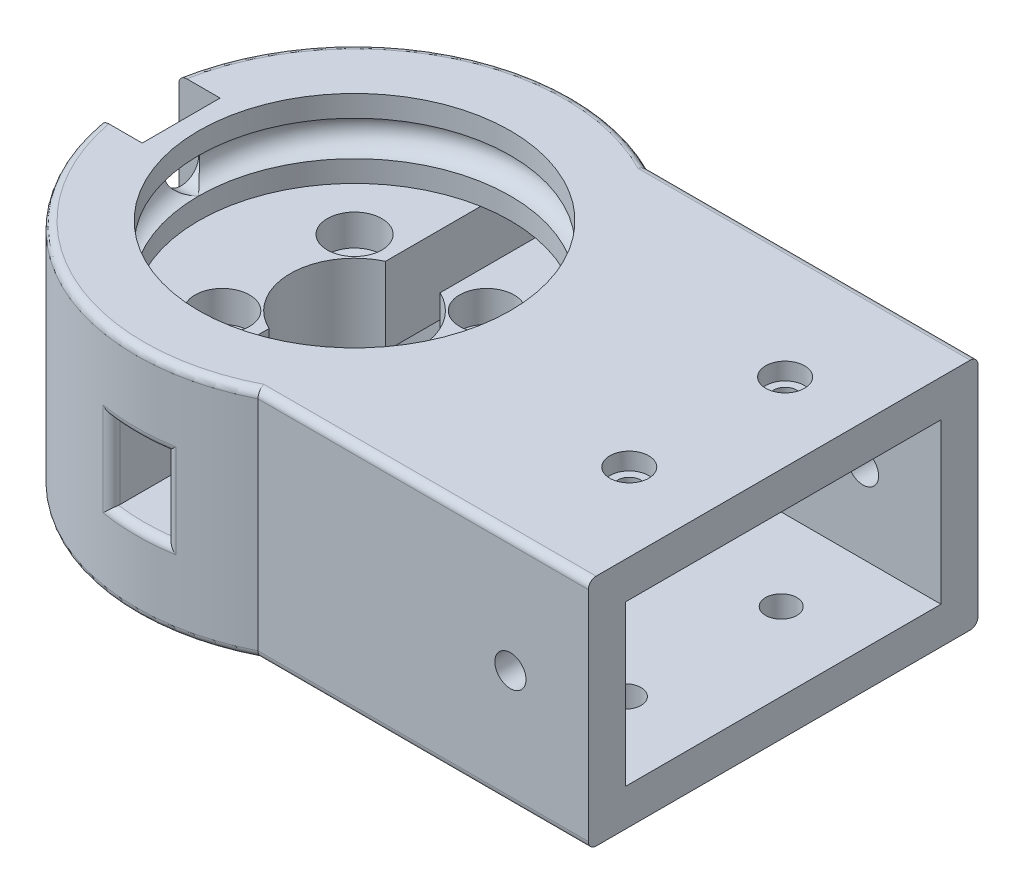
SolidWorks part; units mm, degrees
ref_plane "Front" through (0, 0, 0) normal (0, 0, 1) x (1, 0, 0)
ref_plane "Top" through (0, 0, 0) normal (0, 1, 0) x (1, 0, 0)
ref_plane "Right" through (0, 0, 0) normal (1, 0, 0) x (0, 0, -1)
sketch "Sketch1" plane through (0, 0, 0) normal (0, 0, 1) x (1, 0, 0)
  line L0 (0, -2.25) -> (0, -5)
  line L1 (0, 2.25) -> (0, 5)
  line L2 (0, 5) -> (8, 5)
  line L3 (8, 5) -> (8, -5)
  line L4 (8, -5) -> (0, -5)
  line L6 (-20, 9.1279) -> (-20, -8.1657) construction
  arc A0 (0, -2.25) -> (0, 2.25) centre (0, 0) ccw
revolve "Revolve1" add sketch "Sketch1" angle 360 about L6
sketch "Sketch2" plane through (0, -5, 0) normal (0, -1, 0) x (1, 0, 0)
  circle A0 centre (-20, 0) radius 28
extrude "Boss-Extrude1" add sketch "Sketch2" along normal blind 20
sketch "Sketch3" plane through (0, -25, 0) normal (0, -1, 0) x (1, 0, 0)
  line L1 (-7.3905, 25) -> (45, 25)
  line L3 (-7.3905, -25) -> (45, -25)
  line L4 (45, 25) -> (45, -25)
  arc A0 (-7.3905, -25) -> (-7.3905, 25) centre (-20, 0) ccw
  point P0 (-20, 0)
extrude "Boss-Extrude2" add sketch "Sketch3" against normal blind 30
sketch "Sketch4" plane through (45, 0, 0) normal (1, 0, 0) x (0, 0, -1)
  line L4 (-20.25, 0.25) -> (20.25, 0.25)
  line L5 (-20.25, 0.25) -> (-20.25, -20.25)
  line L6 (-20.25, -20.25) -> (20.25, -20.25)
  line L7 (20.25, 0.25) -> (20.25, -20.25)
  point P6 (0, -10)
extrude "Cut-Extrude2" cut sketch "Sketch4" against normal blind 40
sketch "Sketch5" plane through (0, 5, 0) normal (0, 1, 0) x (1, 0, 0)
  line L0 (45, 25) -> (35, 25)
  line L1 (-7.3905, 25) -> (45, 25) construction
  line L2 (35, 25) -> (35, -25)
  line L3 (45, -25) -> (-7.3905, -25) construction
  line L4 (35, -25) -> (45, -25)
  line L5 (45, -25) -> (45, 25)
extrude "Cut-Extrude3" cut sketch "Sketch5" against normal blind 40
sketch "Sketch6" plane through (0, -20.25, 0) normal (0, 1, 0) x (1, 0, 0)
  circle A0 centre (25, 9.75) radius 2
  circle A1 centre (25, -10.25) radius 2
extrude "Cut-Extrude4" cut sketch "Sketch6" against normal blind 40 and the other way blind 40
sketch "Sketch7" plane through (0, 0, 20.25) normal (0, 0, -1) x (-1, 0, 0)
  circle A0 centre (-25, -10) radius 2
extrude "Cut-Extrude5" cut sketch "Sketch7" against normal blind 45 and the other way blind 50
sketch "Sketch9" plane through (0, -25, 0) normal (0, -1, 0) x (1, 0, 0)
  circle A0 centre (-20, 0) radius 16.5
extrude "Cut-Extrude6" cut sketch "Sketch9" against normal blind 10
sketch "Sketch10" plane through (0, -15, 0) normal (0, -1, 0) x (1, 0, 0)
  circle A0 centre (-20, 0) radius 8.5
extrude "Cut-Extrude7" cut sketch "Sketch10" against normal blind 10
sketch "Sketch11" plane through (0, -15, 0) normal (0, -1, 0) x (1, 0, 0)
  circle A1 centre (-28.4853, 8.4853) radius 2
  circle A2 centre (-28.4853, -8.4853) radius 2
  circle A3 centre (-11.5147, -8.4853) radius 2
  circle A4 centre (-11.5147, 8.4853) radius 2
extrude "Cut-Extrude8" cut sketch "Sketch11" against normal blind 10
sketch "Sketch12" plane through (0, -5, 0) normal (0, 1, 0) x (1, 0, 0)
  circle A0 centre (-28.4853, 8.4853) radius 3.4
  circle A1 centre (-28.4853, -8.4853) radius 3.4
  circle A2 centre (-11.5147, -8.4853) radius 3.4
  circle A3 centre (-11.5147, 8.4853) radius 3.4
extrude "Cut-Extrude10" cut sketch "Sketch12" against normal blind 4
sketch "Sketch14" plane through (0, -5, 0) normal (0, 1, 0) x (1, 0, 0)
  line L1 (-16.5, 30.8966) -> (-23.5, 30.8966)
  line L2 (-16.5, 30.8966) -> (-16.5, -30.8966)
  line L3 (-16.5, -30.8966) -> (-23.5, -30.8966)
  line L4 (-23.5, 30.8966) -> (-23.5, -30.8966)
  line L5 (-16.5, 30.8966) -> (-23.5, -30.8966) construction
  line L6 (-16.5, -30.8966) -> (-23.5, 30.8966) construction
  point P0 (-20, 0)
extrude "Cut-Extrude11" cut sketch "Sketch14" against normal blind 10
ref_plane "Plane2" through (-42.25, 0, 0) normal (1, 0, 0) x (0, 0, -1)
sketch "Sketch15" plane through (0, 0, 0) normal (1, 0, 0) x (0, 0, -1)
  circle A0 centre (0, 0) radius 2.25
extrude "Cut-Extrude12" cut sketch "Sketch15" against normal blind 50
sketch "Sketch16" plane through (-42.25, 0, 0) normal (1, 0, 0) x (0, 0, -1)
  line L1 (5, 31.8439) -> (-5, 31.8439)
  line L2 (5, 31.8439) -> (5, -31.8439)
  line L3 (5, -31.8439) -> (-5, -31.8439)
  line L4 (-5, 31.8439) -> (-5, -31.8439)
  line L5 (5, 31.8439) -> (-5, -31.8439) construction
  line L6 (5, -31.8439) -> (-5, 31.8439) construction
  point P0 (0, 0)
extrude "Cut-Extrude13" cut sketch "Sketch16" against normal blind 50
sketch "Sketch17" plane through (-42.25, 0, 0) normal (-1, 0, 0) x (0, 0, 1)
  line L0 (0, -25) -> (0, -22) construction
  line L1 (5, -25) -> (-5, -25) construction
  circle A0 centre (0, -22) radius 1.5
extrude "Cut-Extrude15" cut sketch "Sketch17" against normal blind 10
sketch "Sketch18" plane through (0, -25, 0) normal (0, -1, 0) x (1, 0, 0)
  circle A0 centre (-20, 0) radius 16.5
  circle A1 centre (-20, 0) radius 16.25
extrude "Boss-Extrude3" add sketch "Sketch18" against normal blind 10
sketch "Sketch19" plane through (0, -15, 0) normal (0, -1, 0) x (1, 0, 0)
  circle A0 centre (-20, 0) radius 8.5
  circle A1 centre (-20, 0) radius 8.25
extrude "Boss-Extrude4" add sketch "Sketch19" against normal blind 10
sketch "Sketch20" plane through (0, -15, 0) normal (0, -1, 0) x (1, 0, 0)
  line L0 (-16.5, -7.746) -> (-16.5, -15.8686) construction
  line L1 (-23.5, 10.3322) -> (-16.5, 10.3322)
  line L2 (-23.5, 10.3322) -> (-23.5, -10.3322)
  line L3 (-23.5, -10.3322) -> (-16.5, -10.3322)
  line L4 (-16.5, 10.3322) -> (-16.5, -10.3322)
  line L5 (-23.5, 10.3322) -> (-16.5, -10.3322) construction
  line L6 (-23.5, -10.3322) -> (-16.5, 10.3322) construction
  point P0 (-20, 0)
extrude "Cut-Extrude16" cut sketch "Sketch20" against normal blind 10
sketch "Sketch21" plane through (0, -5, 0) normal (0, 1, 0) x (1, 0, 0)
  circle A0 centre (-11.5147, 8.4853) radius 3.5
  circle A1 centre (-28.4853, 8.4853) radius 3.5
  circle A2 centre (-28.4853, -8.4853) radius 3.5
  circle A3 centre (-11.5147, -8.4853) radius 3.5
extrude "Cut-Extrude17" cut sketch "Sketch21" against normal blind 4
fillet "Fillet1" radius 1 17 edges at (-20, -25, -16.25) (-32.4822, -25, -25.0638) (-32.4822, -25, 25.0638) (-32.4822, 5, 25.0638) (-32.4822, 5, -25.0638) (-20, -5, -28) (-16.5, -10, -27.7804) (-20, -15, -28) (-23.5, -10, -27.7804) (-20, -5, 28) (-23.5, -10, 27.7804) (-20, -15, 28) (-16.5, -10, 27.7804) (13.8048, -25, 25) (13.8048, -25, -25) (13.8048, 5, -25) (13.8048, 5, 25)
sketch "Sketch23" plane through (0, 5, 0) normal (0, 1, 0) x (1, 0, 0)
  circle A0 centre (25, 9.75) radius 2
  circle A1 centre (25, -10.25) radius 2
extrude "Boss-Extrude5" add sketch "Sketch23" against normal blind 4.75
sketch "Sketch24" plane through (0, 0.25, 0) normal (0, -1, 0) x (1, 0, 0)
  line L0 (35, -20.25) -> (35, -10.25) construction
  line L1 (35, -20.25) -> (35, 20.25) construction
  line L2 (35, -10.25) -> (25, -10.25) construction
  line L3 (25, -10.25) -> (25, 9.75) construction
  circle A0 centre (25, -10.25) radius 1.5
  circle A1 centre (25, 9.75) radius 1.5
extrude "Cut-Extrude18" cut sketch "Sketch24" against normal blind 4.75
sketch "Sketch25" plane through (0, 5, 0) normal (0, 1, 0) x (1, 0, 0)
  circle A0 centre (25, 10.25) radius 2.5
  circle A1 centre (25, -9.75) radius 2.5
extrude "Cut-Extrude19" cut sketch "Sketch25" against normal blind 2.2
